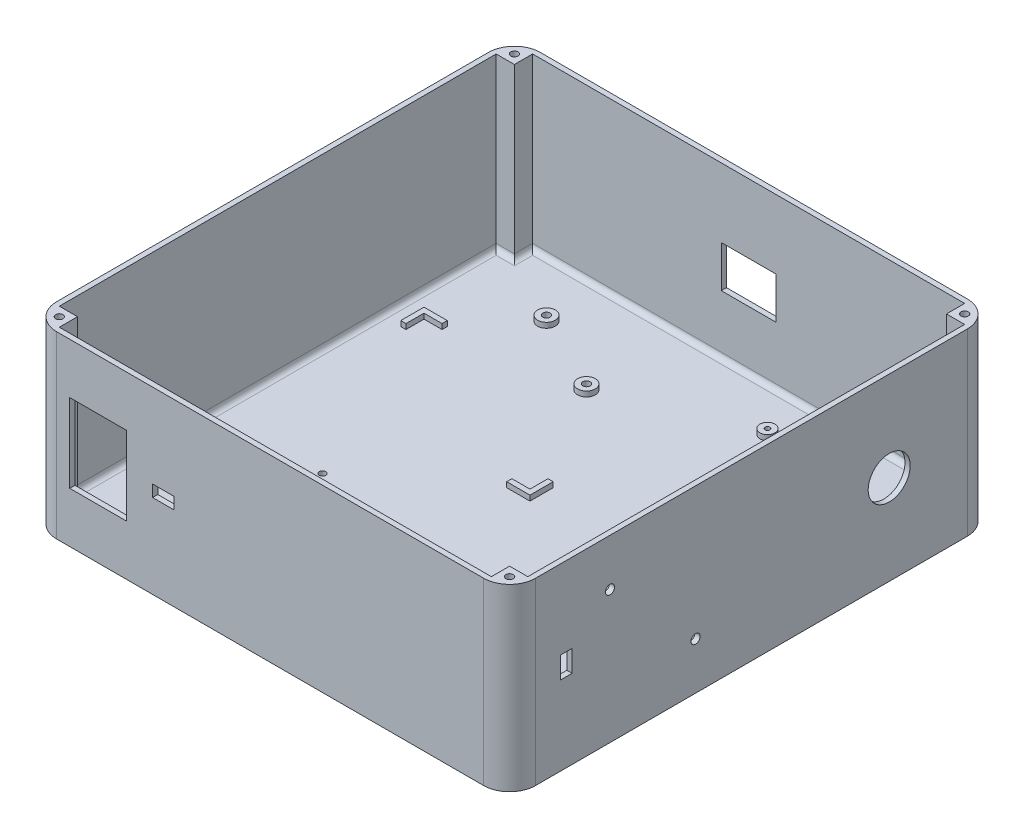
SolidWorks part; units mm, degrees
ref_plane "Front Plane" through (0, 0, 0) normal (0, 0, 1) x (1, 0, 0)
ref_plane "Top Plane" through (0, 0, 0) normal (0, 1, 0) x (1, 0, 0)
ref_plane "Right Plane" through (0, 0, 0) normal (1, 0, 0) x (0, 0, -1)
sketch "Sketch1" plane through (0, 0, 0) normal (0, 1, 0) x (1, 0, 0)
  line L0 (-92, 92.92) -> (-92, -92.92)
  line L1 (-90, 90.92) -> (90, 90.92)
  line L2 (-90, 90.92) -> (-90, -90.92)
  line L3 (-90, -90.92) -> (90, -90.92)
  line L4 (90, 90.92) -> (90, -90.92)
  line L5 (-90, 90.92) -> (90, -90.92) construction
  line L6 (-90, -90.92) -> (90, 90.92) construction
  line L7 (-92, -92.92) -> (92, -92.92)
  line L8 (92, 92.92) -> (92, -92.92)
  line L9 (-92, 92.92) -> (92, 92.92)
  line L10 (-57.851, 69.7) -> (-63.041, 69.7) construction
  line L11 (-80.326, 0.92) -> (29.534, 0.92) construction
  line L12 (-80.326, 0.92) -> (-80.326, -75.92) construction
  line L13 (-80.326, -75.92) -> (29.534, -75.92) construction
  line L14 (29.534, 0.92) -> (29.534, -75.92) construction
  line L15 (34.534, 0.92) -> (80.234, 0.92) construction
  line L16 (34.534, 0.92) -> (34.534, -62.18) construction
  line L17 (34.534, -62.18) -> (80.234, -62.18) construction
  line L18 (80.234, 0.92) -> (80.234, -62.18) construction
  line L19 (-80.326, 46.52) -> (-2.026, 46.52) construction
  line L20 (-80.326, 46.52) -> (-80.326, 8.92) construction
  line L21 (-80.326, 8.92) -> (-2.026, 8.92) construction
  line L22 (-2.026, 46.52) -> (-2.026, 8.92) construction
  line L23 (-63.041, 72.7) -> (-19.311, 72.7) construction
  line L24 (-63.041, 72.7) -> (-63.041, 51.52) construction
  line L25 (-63.041, 51.52) -> (-19.311, 51.52) construction
  line L26 (-19.311, 72.7) -> (-19.311, 51.52) construction
  line L27 (17.234, 80.92) -> (78.234, 80.92) construction
  line L28 (17.234, 80.92) -> (17.234, 22.92) construction
  line L29 (17.234, 22.92) -> (78.234, 22.92) construction
  line L30 (78.234, 80.92) -> (78.234, 22.92) construction
  line L31 (-24.511, 54.52) -> (-19.311, 54.52) construction
  line L32 (23.734, 74.42) -> (72.2367, 26.9227) construction
  line L33 (17.234, 74.42) -> (78.234, 74.42) construction
  line L34 (57.384, 0.92) -> (57.384, -4.08) construction
  line L35 (57.384, -8.96) -> (57.384, -75.267) construction
  line L36 (57.384, -58.45) -> (57.384, -62.18) construction
  line L37 (54.944, -54.01) -> (54.944, -56.01)
  line L38 (59.824, -54.01) -> (59.824, -56.01)
  line L39 (-50.026, -24.01) -> (-80.326, -24.01) construction
  line L40 (-48.776, -22.76) -> (-48.776, 0.92) construction
  line L41 (-12.616, -52.48) -> (-12.616, -75.92) construction
  line L42 (-11.366, -51.23) -> (29.534, -51.23) construction
  line L43 (15.234, 82.92) -> (15.234, 20.92) construction
  line L44 (15.234, 20.92) -> (80.234, 20.92) construction
  line L45 (80.234, 82.92) -> (80.234, 20.92) construction
  line L46 (15.234, 82.92) -> (80.234, 82.92) construction
  line L47 (-41.176, 72.7) -> (-41.176, 51.52) construction
  line L48 (-80.626, 46.82) -> (-80.626, 8.62) construction
  line L49 (-90, 90.92) -> (-83, 90.92)
  line L50 (-90, 90.92) -> (-90, 83.92)
  line L51 (-90, 83.92) -> (-83, 83.92)
  line L52 (-83, 90.92) -> (-83, 83.92)
  line L53 (90, 90.92) -> (83, 90.92)
  line L54 (90, 90.92) -> (90, 83.92)
  line L55 (90, 83.92) -> (83, 83.92)
  line L56 (83, 90.92) -> (83, 83.92)
  line L57 (-90, -90.92) -> (-83, -90.92)
  line L58 (-90, -90.92) -> (-90, -83.92)
  line L59 (-90, -83.92) -> (-83, -83.92)
  line L60 (-83, -90.92) -> (-83, -83.92)
  line L61 (90, -90.92) -> (83, -90.92)
  line L62 (90, -90.92) -> (90, -83.92)
  line L63 (90, -83.92) -> (83, -83.92)
  line L64 (83, -90.92) -> (83, -83.92)
  line L65 (-80.626, 8.62) -> (-1.726, 8.62) construction
  line L66 (-1.726, 46.82) -> (-1.726, 8.62) construction
  line L67 (-80.626, 46.82) -> (-1.726, 46.82) construction
  line L68 (-80.626, 39.8852) -> (-82.626, 39.8852)
  line L69 (-82.626, 39.8852) -> (-82.626, 48.82)
  line L70 (-82.626, 48.82) -> (-73.6912, 48.82)
  line L71 (-73.6912, 48.82) -> (-73.6912, 46.82)
  line L72 (-73.6912, 46.82) -> (-80.626, 46.82)
  line L73 (-80.626, 46.82) -> (-80.626, 39.8852)
  line L74 (-1.726, 15.5548) -> (0.274, 15.5548)
  line L75 (0.274, 15.5548) -> (0.274, 6.62)
  line L76 (0.274, 6.62) -> (-8.6608, 6.62)
  line L77 (-8.6608, 6.62) -> (-8.6608, 8.62)
  line L78 (-8.6608, 8.62) -> (-1.726, 8.62)
  line L79 (-1.726, 8.62) -> (-1.726, 15.5548)
  circle A0 centre (-56.451, 69.7) radius 1.4
  circle A1 centre (-25.911, 54.52) radius 1.4
  circle A2 centre (23.734, 74.42) radius 0.9
  circle A3 centre (72.2367, 26.9227) radius 0.9
  circle A4 centre (57.384, -6.52) radius 2.44
  arc A5 (54.944, -56.01) -> (59.824, -56.01) centre (57.384, -56.01) ccw
  arc A6 (59.824, -54.01) -> (54.944, -54.01) centre (57.384, -54.01) ccw
  circle A7 centre (-48.776, -24.01) radius 1.25
  circle A8 centre (-12.616, -51.23) radius 1.25
  point P0 (0, 0)
  dimension "D4" = 2.8
  dimension "D11" = 1.8
  dimension "D22" = 4.88
  dimension "D23" = 2
  dimension "D26" = 2.5
  dimension "D2" = 21.18
  dimension "D3" = 43.73
  dimension "D5" = 5.19
  dimension "D6" = 5.2
  dimension "D7" = 3
  dimension "D8" = 3
  dimension "D9" = 61
  dimension "D10" = 58
  dimension "D12" = 44.4
  dimension "D13" = 67.886
  dimension "D14" = 6.5
  dimension "D15" = 6.5
  dimension "D16" = 37.6
  dimension "D17" = 78.3
  dimension "D18" = 63.1
  dimension "D19" = 45.7
  dimension "D20" = 5
  dimension "D21" = 3.73
  dimension "D24" = 109.86
  dimension "D25" = 76.84
  dimension "D27" = 23.44
  dimension "D28" = 40.9
  dimension "D29" = 23.68
  dimension "D30" = 30.3
  dimension "D32" = 5
  dimension "D33" = 8
  dimension "D34" = 5
  dimension "D35" = 15
  dimension "D36" = 8
  dimension "D37" = 20
  dimension "D38" = 180
  dimension "D39" = 7
  dimension "D41" = 9.674
  dimension "D42" = 2
  dimension "D1" = 2
  dimension "D31" = 2
  dimension "D40" = 0.3
extrude "Boss-Extrude1" add sketch "Sketch1" along normal blind 65 contours L9 L0 L7 L8 L1 L4 L3 L2 | L50 L49 L52 L51 | L54 L53 L56 L55 | L58 L57 L60 L59 | L62 L61 L64 L63 region at (0, 0, -92.6585)
sketch "Sketch2" plane through (0, 0, 0) normal (0, -1, 0) x (1, 0, 0)
  line L8 (-92, -92.92) -> (92, -92.92)
  line L9 (92, -92.92) -> (92, 92.92)
  line L10 (92, 92.92) -> (-92, 92.92)
  line L11 (-92, 92.92) -> (-92, -92.92)
  line L12 (-92, -92.92) -> (92, -92.92)
  line L13 (92, -92.92) -> (92, 92.92)
  line L14 (92, 92.92) -> (-92, 92.92)
  line L15 (-92, 92.92) -> (-92, -92.92)
  dimension "D1" = 0
extrude "Boss-Extrude2" add sketch "Sketch2" along normal blind 4
sketch "Sketch3" plane through (0, 0, -92.92) normal (0, 0, -1) x (-1, 0, 0)
  line L0 (0, -4) -> (0, 65) construction
  line L1 (92, -4) -> (-92, -4) construction
  line L2 (92, 65) -> (-92, 65) construction
  line L3 (10.515, 22.49) -> (10.515, 38.51)
  line L4 (10.215, 22.79) -> (-10.215, 22.79) construction
  line L5 (10.215, 22.79) -> (10.215, 38.21) construction
  line L6 (10.215, 38.21) -> (-10.215, 38.21) construction
  line L7 (-10.215, 22.79) -> (-10.215, 38.21) construction
  line L8 (10.215, 22.79) -> (-10.215, 38.21) construction
  line L9 (10.215, 38.21) -> (-10.215, 22.79) construction
  line L10 (10.515, 38.51) -> (-10.515, 38.51)
  line L11 (-10.515, 22.49) -> (-10.515, 38.51)
  line L12 (10.515, 22.49) -> (-10.515, 22.49)
  point P6 (0, 30.5)
  dimension "D1" = 20.43
  dimension "D2" = 15.42
  dimension "D3" = 0.3
extrude "Cut-Extrude1" cut sketch "Sketch3" against normal up to next
sketch "Sketch4" plane through (92, 0, 0) normal (1, 0, 0) x (0, 0, -1)
  line L0 (-92.92, 30.5) -> (92.92, 30.5) construction
  line L1 (-65.92, 60) -> (-9.92, 60) construction
  line L2 (-65.92, 60) -> (-65.92, 1) construction
  line L3 (-65.92, 1) -> (-9.92, 1) construction
  line L4 (-9.92, 60) -> (-9.92, 1) construction
  line L5 (-92.92, 65) -> (-92.92, -4) construction
  line L6 (92.92, 65) -> (92.92, -4) construction
  line L7 (-37.92, 1) -> (-37.92, 60) construction
  line L8 (-53.1228, 45.7028) -> (-22.7172, 15.2972) construction
  line L10 (-68.92, 34.65) -> (-73.42, 34.65)
  line L11 (-68.92, 34.65) -> (-68.92, 26.35)
  line L12 (-68.92, 26.35) -> (-73.42, 26.35)
  line L13 (-73.42, 34.65) -> (-73.42, 26.35)
  circle A0 centre (-54.3602, 46.9402) radius 1.75
  circle A1 centre (-21.4798, 14.0598) radius 1.75
  circle A2 centre (52.92, 30.5) radius 7.765 construction
  circle A3 centre (52.92, 30.5) radius 8.065
  point P11 (-37.92, 30.5)
  point P12 (92.92, 30.5)
  dimension "D6" = 3.5
  dimension "D10" = 15.53
  dimension "D1" = 56
  dimension "D2" = 59
  dimension "D3" = 25
  dimension "D4" = 45
  dimension "D5" = 43
  dimension "D7" = 4.5
  dimension "D8" = 8.3
  dimension "D9" = 3
  dimension "D12" = 40
  dimension "D11" = 0.3
extrude "Cut-Extrude4" cut sketch "Sketch4" against normal up to next
sketch "Sketch6" plane through (0, 0, 92.92) normal (0, 0, 1) x (1, 0, 0)
  line L1 (-76.7, 45.3) -> (-55.45, 45.3) construction
  line L2 (-76.7, 45.3) -> (-76.7, 15.7) construction
  line L3 (-76.7, 15.7) -> (-55.45, 15.7) construction
  line L4 (-55.45, 45.3) -> (-55.45, 15.7) construction
  line L5 (-76.7, 45.3) -> (-55.45, 15.7) construction
  line L6 (-76.7, 15.7) -> (-55.45, 45.3) construction
  line L7 (-45.15, 32.75) -> (-36.85, 32.75)
  line L8 (-45.15, 32.75) -> (-45.15, 28.25)
  line L9 (-45.15, 28.25) -> (-36.85, 28.25)
  line L10 (-36.85, 32.75) -> (-36.85, 28.25)
  line L11 (-45.15, 32.75) -> (-36.85, 28.25) construction
  line L12 (-45.15, 28.25) -> (-36.85, 32.75) construction
  line L16 (-77, 45.6) -> (-55.15, 45.6)
  line L17 (-55.15, 45.6) -> (-55.15, 15.4)
  line L18 (-77, 15.4) -> (-55.15, 15.4)
  line L19 (-77, 45.6) -> (-77, 15.4)
  line L20 (-92, 30.5) -> (92, 30.5) construction
  line L21 (-92, 65) -> (-92, -4) construction
  point P0 (-66.075, 30.5)
  point P5 (-41, 30.5)
  dimension "D1" = 4.5
  dimension "D2" = 8.3
  dimension "D3" = 21.25
  dimension "D4" = 29.6
  dimension "D5" = 0.3
  dimension "D6" = 10
  dimension "D7" = 15
extrude "Cut-Extrude3" cut sketch "Sketch6" against normal up to next
sketch "Sketch8" plane through (0, 0, 0) normal (0, 1, 0) x (1, 0, 0)
  line L0 (-90, -90.92) -> (90, -90.92) construction
  line L1 (90, 90.92) -> (90, -90.92) construction
  line L2 (-90, 90.92) -> (-90, -90.92) construction
  line L3 (-90, 90.92) -> (90, 90.92) construction
  line L4 (90, -90.92) -> (83, -90.92) construction
  line L5 (83, -90.92) -> (83, -83.92) construction
  line L6 (90, -83.92) -> (83, -83.92) construction
  line L7 (90, -90.92) -> (90, -83.92) construction
  line L8 (-90, -90.92) -> (-83, -90.92) construction
  line L9 (-83, -90.92) -> (-83, -83.92) construction
  line L10 (-90, -83.92) -> (-83, -83.92) construction
  line L11 (-90, -90.92) -> (-90, -83.92) construction
  line L12 (90, 90.92) -> (83, 90.92) construction
  line L13 (83, 90.92) -> (83, 83.92) construction
  line L14 (90, 83.92) -> (83, 83.92) construction
  line L15 (90, 90.92) -> (90, 83.92) construction
  line L16 (-90, 90.92) -> (-83, 90.92) construction
  line L17 (-83, 90.92) -> (-83, 83.92) construction
  line L18 (-90, 83.92) -> (-83, 83.92) construction
  line L19 (-90, 90.92) -> (-90, 83.92) construction
  line L20 (-92, 92.92) -> (-92, -92.92) construction
  line L21 (-92, -92.92) -> (92, -92.92) construction
  line L22 (92, 92.92) -> (92, -92.92) construction
  line L23 (-92, 92.92) -> (92, 92.92) construction
  line L24 (54.944, -54.01) -> (54.944, -56.01) construction
  line L25 (59.824, -54.01) -> (59.824, -56.01) construction
  line L26 (-1.726, 15.5548) -> (0.274, 15.5548) construction
  line L27 (0.274, 15.5548) -> (0.274, 6.62) construction
  line L28 (0.274, 6.62) -> (-8.6608, 6.62) construction
  line L29 (-8.6608, 6.62) -> (-8.6608, 8.62) construction
  line L30 (-8.6608, 8.62) -> (-1.726, 8.62) construction
  line L31 (-1.726, 8.62) -> (-1.726, 15.5548) construction
  line L32 (-73.6912, 48.82) -> (-73.6912, 46.82) construction
  line L33 (-82.626, 48.82) -> (-73.6912, 48.82) construction
  line L34 (-82.626, 39.8852) -> (-82.626, 48.82) construction
  line L35 (-80.626, 39.8852) -> (-82.626, 39.8852) construction
  line L36 (-80.626, 46.82) -> (-80.626, 39.8852) construction
  line L37 (-73.6912, 46.82) -> (-80.626, 46.82) construction
  line L38 (-90, -90.92) -> (90, -90.92)
  line L39 (90, 90.92) -> (90, -90.92)
  line L40 (-90, 90.92) -> (-90, -90.92)
  line L41 (-90, 90.92) -> (90, 90.92)
  line L42 (90, -90.92) -> (83, -90.92)
  line L43 (83, -90.92) -> (83, -83.92)
  line L44 (90, -83.92) -> (83, -83.92)
  line L45 (90, -90.92) -> (90, -83.92)
  line L46 (-90, -90.92) -> (-83, -90.92)
  line L47 (-83, -90.92) -> (-83, -83.92)
  line L48 (-90, -83.92) -> (-83, -83.92)
  line L49 (-90, -90.92) -> (-90, -83.92)
  line L50 (90, 90.92) -> (83, 90.92)
  line L51 (83, 90.92) -> (83, 83.92)
  line L52 (90, 83.92) -> (83, 83.92)
  line L53 (90, 90.92) -> (90, 83.92)
  line L54 (-90, 90.92) -> (-83, 90.92)
  line L55 (-83, 90.92) -> (-83, 83.92)
  line L56 (-90, 83.92) -> (-83, 83.92)
  line L57 (-90, 90.92) -> (-90, 83.92)
  line L58 (-92, 92.92) -> (-92, -92.92) construction
  line L59 (-92, -92.92) -> (92, -92.92) construction
  line L60 (92, 92.92) -> (92, -92.92) construction
  line L61 (-92, 92.92) -> (92, 92.92) construction
  line L62 (54.944, -54.01) -> (54.944, -56.01) construction
  line L63 (59.824, -54.01) -> (59.824, -56.01) construction
  line L64 (-1.726, 15.5548) -> (0.274, 15.5548)
  line L65 (0.274, 15.5548) -> (0.274, 6.62)
  line L66 (0.274, 6.62) -> (-8.6608, 6.62)
  line L67 (-8.6608, 6.62) -> (-8.6608, 8.62)
  line L68 (-8.6608, 8.62) -> (-1.726, 8.62)
  line L69 (-1.726, 8.62) -> (-1.726, 15.5548)
  line L70 (-73.6912, 48.82) -> (-73.6912, 46.82)
  line L71 (-82.626, 48.82) -> (-73.6912, 48.82)
  line L72 (-82.626, 39.8852) -> (-82.626, 48.82)
  line L73 (-80.626, 39.8852) -> (-82.626, 39.8852)
  line L74 (-80.626, 46.82) -> (-80.626, 39.8852)
  line L75 (-73.6912, 46.82) -> (-80.626, 46.82)
  line L76 (55.244, -54.01) -> (55.244, -56.01)
  line L77 (59.524, -54.01) -> (59.524, -56.01)
  circle A0 centre (-56.451, 69.7) radius 1.4 construction
  circle A1 centre (57.384, -6.52) radius 2.44 construction
  circle A2 centre (72.2367, 26.9227) radius 0.9 construction
  circle A3 centre (23.734, 74.42) radius 0.9 construction
  circle A4 centre (-25.911, 54.52) radius 1.4 construction
  circle A5 centre (-12.616, -51.23) radius 1.25 construction
  circle A6 centre (-48.776, -24.01) radius 1.25 construction
  arc A7 (54.944, -56.01) -> (59.824, -56.01) centre (57.384, -56.01) ccw construction
  arc A8 (59.824, -54.01) -> (54.944, -54.01) centre (57.384, -54.01) ccw construction
  circle A9 centre (-56.451, 69.7) radius 1.4
  circle A10 centre (57.384, -6.52) radius 2.44 construction
  circle A11 centre (72.2367, 26.9227) radius 0.9
  circle A12 centre (23.734, 74.42) radius 0.9
  circle A13 centre (-25.911, 54.52) radius 1.4
  circle A14 centre (-12.616, -51.23) radius 1.25
  circle A15 centre (-48.776, -24.01) radius 1.25
  arc A16 (54.944, -56.01) -> (59.824, -56.01) centre (57.384, -56.01) ccw construction
  arc A17 (59.824, -54.01) -> (54.944, -54.01) centre (57.384, -54.01) ccw construction
  circle A18 centre (-56.451, 69.7) radius 3.4
  circle A19 centre (-25.911, 54.52) radius 3.4
  circle A20 centre (23.734, 74.42) radius 2.9
  circle A21 centre (72.2367, 26.9227) radius 2.9
  circle A22 centre (57.384, -6.52) radius 2.14
  arc A23 (55.244, -56.01) -> (59.524, -56.01) centre (57.384, -56.01) ccw
  arc A24 (59.524, -54.01) -> (55.244, -54.01) centre (57.384, -54.01) ccw
  dimension "D1" = 2
  dimension "D2" = 0.3
extrude "Boss-Extrude3" add sketch "Sketch8" along normal blind 2 contours L75 L70 L71 L72 L73 L74 | A18 A9 | A19 A13 | A20 A12 | A21 A11 | L66 L67 L68 L69 L64 L65 region at (-73.8176, 0, -47.82) region at (-59.7548, 0, -69.7) region at (-29.2148, 0, -54.52) region at (20.916, 0, -74.42) region at (69.4187, 0, -26.9227)
extrude "Boss-Extrude4" add sketch "Sketch8<3>" along normal blind 4 contours A22 | L77 A24 L76 A23 region at (57.384, 0, 55.01) region at (57.384, 0, 6.52)
sketch "Sketch8<3>" plane through (0, 0, 0) normal (0, 1, 0) x (1, 0, 0) same geometry as "Sketch8"
extrude "Cut-Extrude5" cut sketch "Sketch8<4>" against normal up to next contours A15 | A14 region at (-12.616, 0, 51.23) region at (-48.776, 0, 24.01)
sketch "Sketch8<4>" plane through (0, 0, 0) normal (0, 1, 0) x (1, 0, 0) same geometry as "Sketch8"
sketch "Sketch9" plane through (0, -4, 0) normal (0, -1, 0) x (1, 0, 0)
  circle A0 centre (-12.616, 51.23) radius 1.25 construction
  circle A1 centre (-48.776, 24.01) radius 1.25 construction
  circle A8 centre (-12.616, 51.23) radius 1.25
  circle A9 centre (-48.776, 24.01) radius 1.25
  circle A10 centre (-12.616, 51.23) radius 2.25
  circle A11 centre (-48.776, 24.01) radius 2.25
  dimension "D1" = 1
extrude "Cut-Extrude6" cut sketch "Sketch9" against normal blind 1.5 contours A10 | A11
sketch "Sketch10" plane through (0, 65, 0) normal (0, 1, 0) x (1, 0, 0)
  line L0 (-90, 87.42) -> (-83, 87.42) construction
  line L1 (-83, 83.92) -> (-90, 83.92) construction
  line L2 (-83, 83.92) -> (-83, 90.92) construction
  line L3 (-83, 90.92) -> (-90, 90.92) construction
  line L4 (-90, 83.92) -> (-90, 90.92) construction
  line L5 (83, 83.92) -> (90, 83.92) construction
  line L6 (83, 83.92) -> (83, 90.92) construction
  line L7 (83, 90.92) -> (90, 90.92) construction
  line L8 (90, 83.92) -> (90, 90.92) construction
  line L9 (-83, -83.92) -> (-90, -83.92) construction
  line L10 (-83, -83.92) -> (-83, -90.92) construction
  line L11 (-83, -90.92) -> (-90, -90.92) construction
  line L12 (-90, -83.92) -> (-90, -90.92) construction
  line L13 (83, -83.92) -> (90, -83.92) construction
  line L14 (83, -83.92) -> (83, -90.92) construction
  line L15 (83, -90.92) -> (90, -90.92) construction
  line L16 (90, -83.92) -> (90, -90.92) construction
  line L17 (83, 87.42) -> (90, 87.42) construction
  line L18 (-90, -87.42) -> (-83, -87.42) construction
  line L19 (83, -87.42) -> (90, -87.42) construction
  circle A0 centre (-86.5, 87.42) radius 1.4
  circle A1 centre (86.5, 87.42) radius 1.4
  circle A2 centre (86.5, -87.42) radius 1.4
  circle A3 centre (-86.5, -87.42) radius 1.4
  dimension "D2" = 2.8
  dimension "D1" = 7
extrude "Cut-Extrude7" cut sketch "Sketch10" against normal blind 4
fillet "Fillet1" radius 10 4 edges at (92, 30.5, 92.92) (-92, 30.5, -92.92) (92, 30.5, -92.92) (-92, 30.5, 92.92)
fillet "Fillet2" radius 2 12 edges at (86.5, 0, 83.92) (83, 0, 87.42) (83, 0, -87.42) (86.5, 0, -83.92) (-83, 0, -87.42) (-86.5, 0, -83.92) (-83, 0, 87.42) (-86.5, 0, 83.92) (0, 0, 90.92) (90, 0, 0) (0, 0, -90.92) (-90, 0, 0)
sketch "Sketch11" plane through (0, -4, 0) normal (0, -1, 0) x (1, 0, 0)
  line L0 (0, -92.92) -> (0, 92.92) construction
  line L1 (-82, -92.92) -> (82, -92.92) construction
  line L2 (82, 92.92) -> (-82, 92.92) construction
  line L4 (25, -25) -> (-25, -25) construction
  line L5 (25, -25) -> (25, 25) construction
  line L6 (25, 25) -> (-25, 25) construction
  line L7 (-25, -25) -> (-25, 25) construction
  line L8 (25, -25) -> (-25, 25) construction
  line L9 (25, 25) -> (-25, -25) construction
  circle A0 centre (25, -25) radius 1.4
  circle A1 centre (-25, -25) radius 1.4
  circle A2 centre (25, 25) radius 1.4
  circle A3 centre (-25, 25) radius 1.4
  point P6 (0, 0)
  dimension "D2" = 2.8
  dimension "D1" = 50
extrude "Cut-Extrude8" cut sketch "Sketch11" against normal blind 2.5
